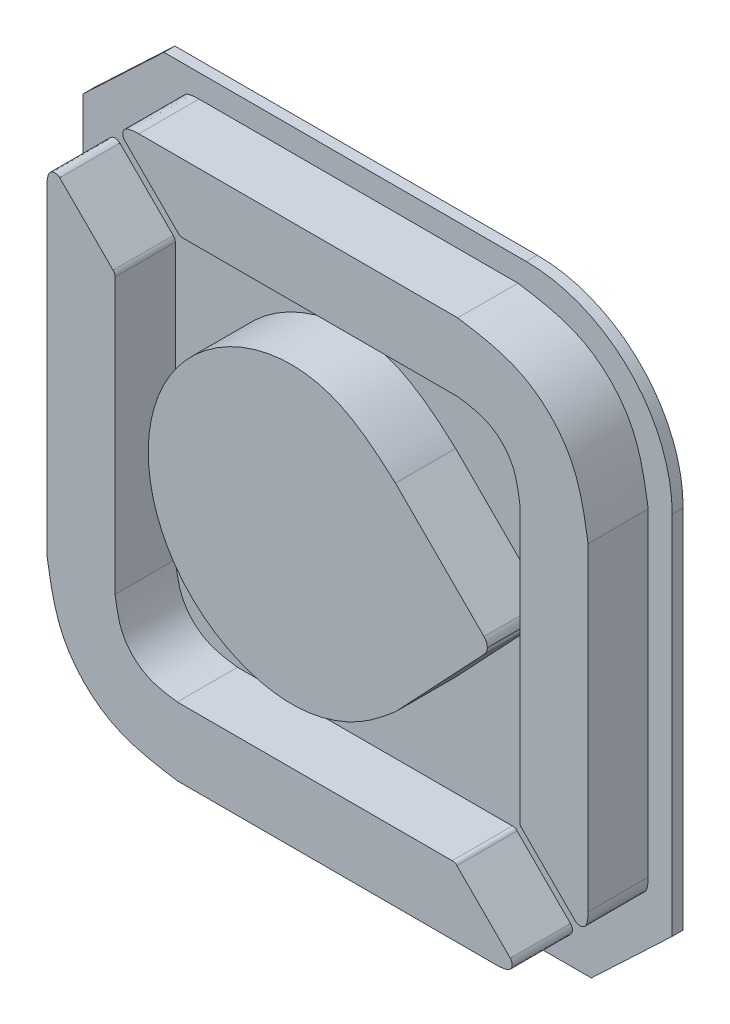
SolidWorks part; units mm, degrees
ref_plane "Front Plane" through (0, 0, 0) normal (0, 0, 1) x (1, 0, 0)
ref_plane "Top Plane" through (0, 0, 0) normal (0, 1, 0) x (1, 0, 0)
ref_plane "Right Plane" through (0, 0, 0) normal (1, 0, 0) x (0, 0, -1)
sketch "Sketch1" plane through (0, 0, 0) normal (0, 0, 1) x (1, 0, 0)
  line L0 (25.2291, 14.0424) -> (20.3759, 18.8958)
  line L1 (20.3759, 8.0409) -> (25.2291, 13.1908)
  line L2 (27.1958, 21.3046) -> (27.1958, 6.2259)
  line L3 (27.3058, 5.9655) -> (30.2329, 3.0385)
  line L4 (30.937, 3.8171) -> (30.937, 21.3046)
  line L5 (23.7875, 28.4536) -> (6.3004, 28.4522)
  line L6 (5.5233, 27.748) -> (8.4502, 24.8225)
  line L7 (8.7092, 24.711) -> (23.7875, 24.7124)
  line L8 (5.0008, 5.9285) -> (5.0008, 21.0069)
  line L9 (4.8893, 21.2673) -> (1.9623, 24.1943)
  line L10 (1.2582, 23.4157) -> (1.2582, 5.9285)
  line L11 (8.4089, -1.2209) -> (25.8947, -1.2194)
  line L12 (26.6719, -0.5153) -> (23.7449, 2.4117)
  line L13 (23.486, 2.5218) -> (8.4089, 2.5206)
  spline S0 degree 3 poles (25.4139, 13.5985) (25.4088, 13.6512) (25.3983, 13.7596) (25.3345, 13.9138) (25.264, 13.9998) (25.2291, 14.0424) knots 0 0 0 0 0.322338 0.663828 1 1 1 1
  spline S1 degree 3 poles (20.3759, 18.8958) (20.3717, 18.9003) (20.3636, 18.909) (20.3511, 18.9214) (19.8448, 19.3799) (18.7994, 20.2734) (16.9951, 21.3735) (14.1721, 21.9313) (10.6368, 20.8891) (7.5748, 17.8214) (6.4314, 13.6015) (7.5726, 9.3846) (10.6409, 6.3295) (14.1614, 5.3209) (16.9564, 5.8315) (18.83, 6.7454) (19.8725, 7.619) (20.3759, 8.0409) knots 0 0 0 0 0.000489 0.000958 0.001407 0.055155 0.111027 0.168427 0.280644 0.38981 0.50219 0.614354 0.723171 0.835316 0.891384 0.947546 1 1 1 1
  spline S2 degree 3 poles (25.2291, 13.1908) (25.2629, 13.2299) (25.3299, 13.3072) (25.3992, 13.447) (25.409, 13.548) (25.4139, 13.5985) knots 0 0 0 0 0.338885 0.669777 1 1 1 1
  spline S3 degree 3 poles (27.1958, 6.2259) (27.1975, 6.2038) (27.2008, 6.1604) (27.2084, 6.0952) (27.2344, 6.046) (27.2599, 6.0101) (27.2833, 5.9867) (27.2984, 5.9724) (27.3058, 5.9655) knots 0 0 0 0 0.227493 0.445972 0.663373 0.787115 0.896006 1 1 1 1
  spline S4 degree 3 poles (30.2329, 3.0385) (30.2721, 3.0095) (30.3508, 2.9515) (30.499, 2.9275) (30.6349, 2.9547) (30.7444, 3.0221) (30.8233, 3.1125) (30.8727, 3.2455) (30.905, 3.4056) (30.9383, 3.5907) (30.9358, 3.7211) (30.9373, 3.7924) (30.9379, 3.8048) (30.9373, 3.813) (30.937, 3.8171) knots 0 0 0 0 0.104345 0.208931 0.313565 0.397995 0.482811 0.567894 0.701187 0.836715 0.973247 0.982163 0.991064 1 1 1 1
  spline S5 degree 3 poles (30.937, 21.3046) (30.7375, 22.5535) (30.3435, 25.0196) (27.503, 27.8601) (25.0367, 28.2541) (23.7875, 28.4536) knots 0 0 0 0 0.336154 0.663772 1 1 1 1
  spline S6 degree 3 poles (6.3004, 28.4522) (6.2964, 28.4525) (6.2885, 28.4531) (6.2767, 28.4525) (6.2055, 28.4509) (6.0749, 28.4539) (5.8894, 28.4201) (5.7285, 28.3904) (5.5965, 28.3388) (5.5062, 28.2602) (5.4382, 28.151) (5.4109, 28.0148) (5.4352, 27.8662) (5.494, 27.7874) (5.5233, 27.748) knots 0 0 0 0 0.008622 0.017031 0.025643 0.162638 0.298245 0.431901 0.516392 0.601007 0.685957 0.790142 0.895037 1 1 1 1
  spline S7 degree 3 poles (8.4502, 24.8225) (8.4595, 24.8135) (8.4777, 24.796) (8.5047, 24.7688) (8.5402, 24.7401) (8.5893, 24.7201) (8.6486, 24.7106) (8.6885, 24.7108) (8.7092, 24.711) knots 0 0 0 0 0.131285 0.25763 0.390972 0.594165 0.788898 1 1 1 1
  spline S8 degree 3 poles (23.7875, 24.7124) (24.3914, 24.6242) (25.5718, 24.4517) (26.9348, 23.0897) (27.1075, 21.909) (27.1958, 21.3046) knots 0 0 0 0 0.33841 0.661392 1 1 1 1
  spline S9 degree 3 poles (5.0008, 21.0069) (5, 21.026) (4.9987, 21.0611) (4.9902, 21.1151) (4.9699, 21.1594) (4.9462, 21.1994) (4.9201, 21.2339) (4.8999, 21.2558) (4.8893, 21.2673) knots 0 0 0 0 0.196746 0.361608 0.557262 0.692766 0.839563 1 1 1 1
  spline S10 degree 3 poles (1.9623, 24.1943) (1.923, 24.2232) (1.8443, 24.2812) (1.6962, 24.3053) (1.5602, 24.2781) (1.4508, 24.2104) (1.3721, 24.12) (1.3221, 23.9875) (1.2896, 23.8274) (1.2593, 23.6424) (1.2538, 23.5118) (1.259, 23.4405) (1.2584, 23.428) (1.2582, 23.4198) (1.2582, 23.4157) knots 0 0 0 0 0.104385 0.20895 0.313569 0.398093 0.483012 0.567612 0.700915 0.836485 0.973043 0.982112 0.991066 1 1 1 1
  spline S11 degree 3 poles (1.2582, 5.9285) (1.4578, 4.6795) (1.8521, 2.2131) (4.6929, -0.628) (7.1596, -1.0215) (8.4089, -1.2209) knots 0 0 0 0 0.336157 0.663806 1 1 1 1
  spline S12 degree 3 poles (25.8947, -1.2194) (25.8988, -1.2197) (25.9071, -1.2203) (25.9196, -1.2197) (25.991, -1.2182) (26.1215, -1.2208) (26.3065, -1.1874) (26.4666, -1.1555) (26.5991, -1.1055) (26.6895, -1.0269) (26.7571, -0.9175) (26.7843, -0.7815) (26.7599, -0.633) (26.7013, -0.5545) (26.6719, -0.5153) knots 0 0 0 0 0.008953 0.017947 0.027021 0.163491 0.298949 0.432165 0.516776 0.601601 0.686035 0.790672 0.895263 1 1 1 1
  spline S13 degree 3 poles (23.7449, 2.4117) (23.7357, 2.4212) (23.7176, 2.4401) (23.6898, 2.4687) (23.6566, 2.4991) (23.6071, 2.5159) (23.5486, 2.5206) (23.5077, 2.5213) (23.486, 2.5218) knots 0 0 0 0 0.134582 0.264928 0.404991 0.586048 0.77989 1 1 1 1
  spline S14 degree 3 poles (8.4089, 2.5206) (7.8048, 2.6086) (6.6242, 2.7804) (5.2615, 4.1433) (5.089, 5.3241) (5.0008, 5.9285) knots 0 0 0 0 0.338406 0.661372 1 1 1 1
extrude "Boss-Extrude1" add sketch "Sketch1" along normal blind 3.9
sketch "Sketch2" plane through (0, 0, 0) normal (0, 0, 1) x (1, 0, 0)
  line L0 (4.38, 29.7109) -> (-0.0558, 25.5178)
  line L1 (7.9442, -2.5341) -> (27.8152, -2.5341)
  line L2 (-0.0558, 5.4659) -> (-0.0558, 25.5178)
  line L3 (4.38, 29.7109) -> (24.251, 29.7109)
  line L4 (32.251, 1.6589) -> (32.251, 21.7109)
  line L5 (32.251, 1.6589) -> (27.8152, -2.5341)
  line L6 (1.2582, 14.6721) -> (-0.0558, 14.6721) construction
  line L7 (1.2582, 23.4157) -> (1.2582, 5.9285) construction
  line L8 (17.1518, -1.2201) -> (17.1518, -2.5341) construction
  line L9 (8.4089, -1.2209) -> (25.8947, -1.2194) construction
  line L10 (30.937, 12.5609) -> (32.251, 12.5609) construction
  line L11 (30.937, 3.8171) -> (30.937, 21.3046) construction
  line L12 (15.044, 28.4529) -> (15.4236, 29.7109) construction
  line L13 (23.7875, 28.4536) -> (6.3004, 28.4522) construction
  arc A0 (24.251, 29.7109) -> (32.251, 21.7109) centre (24.251, 21.7109) cw
  arc A2 (7.9442, -2.5341) -> (-0.0558, 5.4659) centre (7.9442, 5.4659) cw
  dimension "D1" = 8
  dimension "D3" = 8
extrude "Boss-Extrude2" add sketch "Sketch2" along normal blind 0.6
